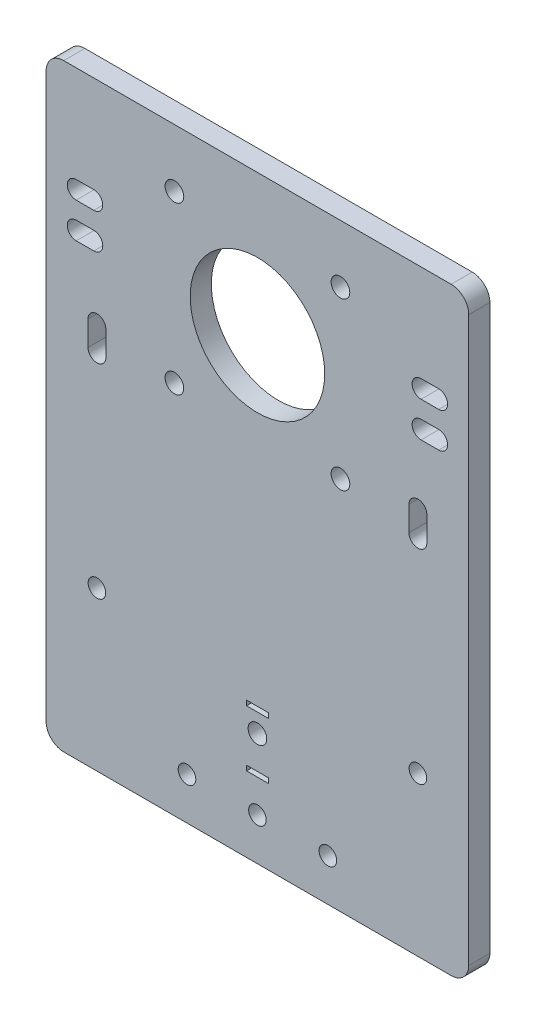
SolidWorks part; units mm, degrees
ref_plane "Front Plane" through (0, 0, 0) normal (0, 0, 1) x (1, 0, 0)
ref_plane "Top Plane" through (0, 0, 0) normal (0, 1, 0) x (1, 0, 0)
ref_plane "Right Plane" through (0, 0, 0) normal (1, 0, 0) x (0, 0, -1)
sketch "Sketch1" plane through (0, 0, 0) normal (0, 0, 1) x (1, 0, 0)
  line L1 (-55, -85) -> (55, -85)
  line L2 (-60, -80) -> (-60, 80)
  line L3 (-55, 85) -> (55, 85)
  line L4 (60, -80) -> (60, 80)
  line L5 (-60, -85) -> (60, 85) construction
  line L6 (-60, 85) -> (60, -85) construction
  arc A0 (-55, -85) -> (-60, -80) centre (-55, -80) cw
  arc A1 (55, -85) -> (60, -80) centre (55, -80) ccw
  arc A2 (55, 85) -> (60, 80) centre (55, 80) cw
  arc A3 (-60, 80) -> (-55, 85) centre (-55, 80) cw
  point P0 (0, 0)
  dimension "D3" = 5
  dimension "D1" = 170
  dimension "D2" = 120
extrude "Boss-Extrude1" add sketch "Sketch1" along normal blind 6
sketch "Sketch3" plane through (0, 0, 6) normal (0, 0, 1) x (1, 0, 0)
  line L0 (55, 85) -> (-55, 85) construction
  circle A0 centre (0, 45) radius 19.1
  point P6 (0, 85)
  dimension "D1" = 40
  dimension "D2" = 38.2
extrude "Cut-Extrude1" cut sketch "Sketch3" against normal blind 6
hole_wizard "M5 Clearance Hole1" positions "Sketch8" profile "Sketch9" hole size "M5" standard "ANSI Metric" end condition through all
sketch "Sketch8" plane through (0, 0, 6) normal (0, 0, 1) x (1, 0, 0)
  circle A0 centre (0, 45) radius 19.1 construction
  point P0 (-23.57, 68.57)
  point P2 (23.57, 68.57)
  point P4 (23.57, 21.43)
  point P6 (-23.57, 21.43)
  dimension "D2" = 23.57
  dimension "D3" = 23.57
  dimension "D4" = 23.57
  dimension "D5" = 23.57
  dimension "D1" = 23.57
sketch "Sketch9" plane through (-23.57, 68.57, 6) normal (1, 0, 0) x (0, -1, 0)
  line L0 (0, 0) -> (0, 6)
  line L1 (0, 6) -> (2.65, 6)
  line L2 (2.65, 6) -> (2.65, 0)
  line L5 (2.65, 0) -> (0, 0)
  line L11 (0, -6.35) -> (0, 107.95) construction
  dimension "Thru Hole Dia." = 5.3
  dimension "Thru Hole Depth" = 6
sketch "Sketch11" plane through (0, 0, 6) normal (0, 0, 1) x (1, 0, 0)
  line L0 (-45.57, 24.93) -> (-45.57, 17.93) construction
  line L1 (-43.03, 24.93) -> (-43.03, 17.93)
  line L2 (-48.11, 24.93) -> (-48.11, 17.93)
  line L5 (0, 63.1141) -> (0, -86.0691) construction
  line L8 (45.57, 24.93) -> (45.57, 17.93) construction
  line L9 (43.03, 24.93) -> (43.03, 17.93)
  line L10 (48.11, 24.93) -> (48.11, 17.93)
  arc A0 (-43.03, 24.93) -> (-48.11, 24.93) centre (-45.57, 24.93) ccw
  arc A1 (-48.11, 17.93) -> (-43.03, 17.93) centre (-45.57, 17.93) ccw
  circle A3 centre (-23.57, 21.43) radius 2.65 construction
  arc A4 (43.03, 24.93) -> (48.11, 24.93) centre (45.57, 24.93) cw
  arc A5 (48.11, 17.93) -> (43.03, 17.93) centre (45.57, 17.93) cw
  point P2 (-45.57, 21.43)
  point P15 (45.57, 21.43)
  dimension "D2" = 2.54
  dimension "D1" = 7
  dimension "D3" = 22
extrude "Cut-Extrude2" cut sketch "Sketch11" against normal blind 6
sketch "Sketch15" plane through (0, 0, 6) normal (0, 0, 1) x (1, 0, 0)
  line L0 (-51.46, 45) -> (-46.46, 45) construction
  line L1 (-51.46, 47.54) -> (-46.46, 47.54)
  line L2 (-51.46, 42.46) -> (-46.46, 42.46)
  line L3 (-51.46, 55) -> (-46.46, 55) construction
  line L4 (-51.46, 57.54) -> (-46.46, 57.54)
  line L5 (-51.46, 52.46) -> (-46.46, 52.46)
  line L6 (-60, 80) -> (-60, -80) construction
  line L8 (55, 85) -> (-55, 85) construction
  line L9 (0, 75.2932) -> (0, -13.323) construction
  line L10 (0, 63.1141) -> (0, -86.0691) construction
  line L11 (51.46, 45) -> (46.46, 45) construction
  line L12 (51.46, 47.54) -> (46.46, 47.54)
  line L13 (51.46, 42.46) -> (46.46, 42.46)
  line L14 (51.46, 55) -> (46.46, 55) construction
  line L15 (51.46, 57.54) -> (46.46, 57.54)
  line L16 (51.46, 52.46) -> (46.46, 52.46)
  arc A0 (-51.46, 47.54) -> (-51.46, 42.46) centre (-51.46, 45) ccw
  arc A1 (-46.46, 42.46) -> (-46.46, 47.54) centre (-46.46, 45) ccw
  arc A2 (-51.46, 57.54) -> (-51.46, 52.46) centre (-51.46, 55) ccw
  arc A3 (-46.46, 52.46) -> (-46.46, 57.54) centre (-46.46, 55) ccw
  arc A5 (51.46, 47.54) -> (51.46, 42.46) centre (51.46, 45) cw
  arc A6 (46.46, 42.46) -> (46.46, 47.54) centre (46.46, 45) cw
  arc A7 (51.46, 57.54) -> (51.46, 52.46) centre (51.46, 55) cw
  arc A8 (46.46, 52.46) -> (46.46, 57.54) centre (46.46, 55) cw
  point P2 (-48.96, 45)
  point P7 (-48.96, 55)
  point P15 (-54, 45)
  point P32 (48.96, 45)
  point P39 (48.96, 55)
  dimension "D1" = 30
  dimension "D2" = 2.54
  dimension "D4" = 5
  dimension "D5" = 6
  dimension "D6" = 10
extrude "Cut-Extrude4" cut sketch "Sketch15" against normal blind 6
hole_wizard "Ø5.0 (5) Diameter Hole4" positions "Sketch17" profile "Sketch18" hole size "Ø5.0" standard "ANSI Metric" end condition through all
sketch "Sketch17" plane through (0, 0, 6) normal (0, 0, 1) x (1, 0, 0)
  line L1 (-55, -85) -> (55, -85) construction
  line L2 (60, -80) -> (60, 80) construction
  line L3 (-60, 80) -> (-60, -80) construction
  point P0 (-45.57, -39.97)
  point P2 (45.57, -39.97)
  point P4 (20, -73)
  point P6 (0, -73)
  point P8 (-20, -73)
  dimension "D3" = 40
  dimension "D1" = 61.4
  dimension "D2" = 12
  dimension "D4" = 40
sketch "Sketch18" plane through (-45.57, -39.97, 6) normal (1, 0, 0) x (0, -1, 0)
  line L0 (0, 0) -> (0, 6)
  line L1 (0, 6) -> (2.5, 6)
  line L2 (2.5, 6) -> (2.5, 0)
  line L5 (2.5, 0) -> (0, 0)
  line L11 (0, -6.35) -> (0, 107.95) construction
  dimension "Thru Hole Dia." = 5
  dimension "Thru Hole Depth" = 6
hole_wizard "M5 Clearance Hole2" positions "Sketch19" profile "Sketch20" hole size "M5" standard "ANSI Metric"
sketch "Sketch19" plane through (0, 0, 0) normal (0, 0, -1) x (-1, 0, 0)
  circle A0 centre (0, -73) radius 2.5 construction
  point P0 (0, -53)
  dimension "D1" = 20
sketch "Sketch20" plane through (0, -53, 0) normal (1, 0, 0) x (0, 1, 0)
  line L0 (0, 0) -> (0, 11.5923)
  line L1 (0, 11.5923) -> (2.65, 10)
  line L2 (2.65, 10) -> (2.65, 0)
  line L5 (2.65, 0) -> (0, 0)
  line L10 (0, 11.5923) -> (-2.65, 10) construction
  line L11 (0, -6.35) -> (0, 107.95) construction
  dimension "Hole Dia." = 5.3
  dimension "Hole Depth" = 10
  dimension "Drill Angle" = 118
sketch "Sketch21" plane through (0, 0, 0) normal (0, 0, -1) x (-1, 0, 0)
  line L1 (-3.1, -46.3) -> (3.1, -46.3)
  line L2 (-3.1, -46.3) -> (-3.1, -47.7)
  line L3 (-3.1, -47.7) -> (3.1, -47.7)
  line L4 (3.1, -46.3) -> (3.1, -47.7)
  line L5 (-3.1, -46.3) -> (3.1, -47.7) construction
  line L6 (-3.1, -47.7) -> (3.1, -46.3) construction
  circle A0 centre (0, -53) radius 2.65 construction
  point P0 (0, -47)
  point P5 (0, 0)
  dimension "D1" = 6.2
  dimension "D2" = 1.4
  dimension "D3" = 6
extrude "Cut-Extrude5" cut sketch "Sketch21" against normal blind 6
sketch "Sketch22" plane through (0, 0, 6) normal (0, 0, 1) x (1, 0, 0)
  line L1 (-3.1, -63.7) -> (3.1, -63.7)
  line L2 (-3.1, -63.7) -> (-3.1, -62.3)
  line L3 (-3.1, -62.3) -> (3.1, -62.3)
  line L4 (3.1, -63.7) -> (3.1, -62.3)
  line L5 (-3.1, -63.7) -> (3.1, -62.3) construction
  line L6 (-3.1, -62.3) -> (3.1, -63.7) construction
  circle A0 centre (0, -53) radius 2.65 construction
  point P0 (0, -63)
  point P5 (0, 0)
  dimension "D1" = 6.2
  dimension "D2" = 1.4
  dimension "D3" = 10
extrude "Cut-Extrude6" cut sketch "Sketch22" against normal blind 10
